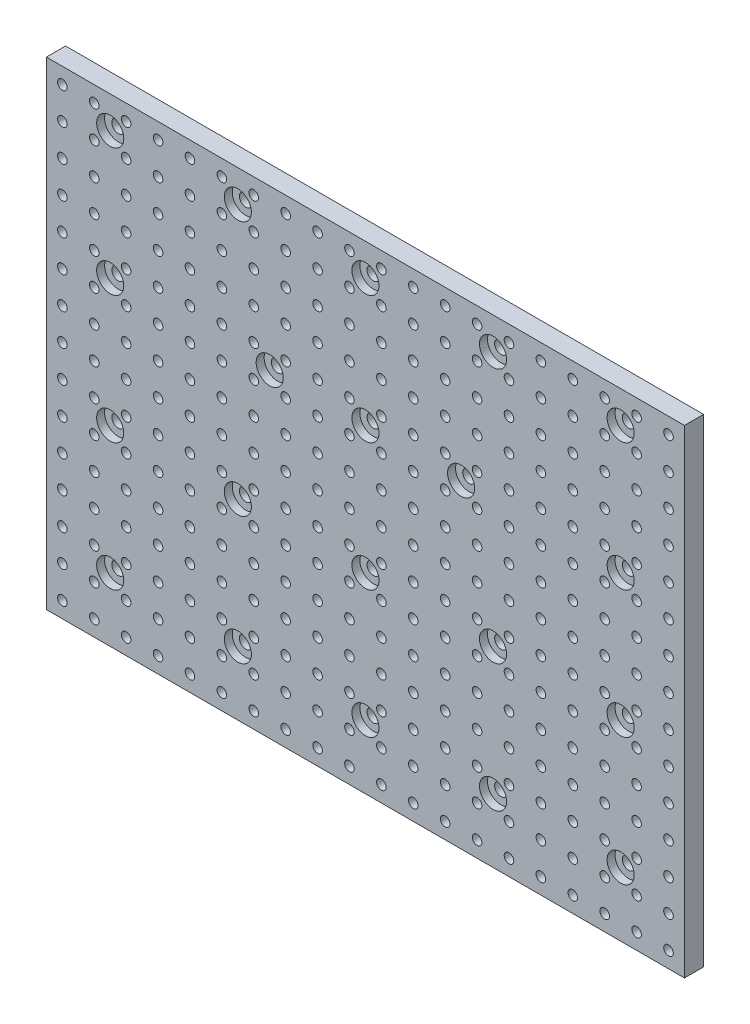
SolidWorks part; units mm, degrees
ref_plane "Front Plane" through (0, 0, 0) normal (0, 0, 1) x (1, 0, 0)
ref_plane "Top Plane" through (0, 0, 0) normal (0, 1, 0) x (1, 0, 0)
ref_plane "Right Plane" through (0, 0, 0) normal (1, 0, 0) x (0, 0, -1)
sketch "Sketch1" plane through (0, 0, 0) normal (0, 0, 1) x (1, 0, 0)
  line L1 (-200, 150) -> (200, 150)
  line L2 (-200, 150) -> (-200, -150)
  line L3 (-200, -150) -> (200, -150)
  line L4 (200, 150) -> (200, -150)
  line L5 (0, -150) -> (0, 150) construction
  line L6 (-200, 0) -> (200, 0) construction
  point P0 (0, 0)
  dimension "D1" = 300
  dimension "D2" = 400
extrude "Boss-Extrude1" add sketch "Sketch1" along normal blind 12
sketch "Sketch3" plane through (0, 0, 12) normal (0, 0, 1) x (1, 0, 0)
  circle A0 centre (-116, 92.75) radius 5
  circle A1 centre (-84, 92.75) radius 5
  circle A2 centre (-116, 56.75) radius 5
  circle A3 centre (-84, 56.75) radius 5
  circle A4 centre (84, 92.75) radius 5
  circle A5 centre (116, 92.75) radius 5
  circle A6 centre (84, 56.75) radius 5
  circle A7 centre (116, 56.75) radius 5
  circle A8 centre (116, -56.75) radius 5
  circle A9 centre (84, -56.75) radius 5
  circle A10 centre (84, -92.75) radius 5
  circle A11 centre (116, -92.75) radius 5
  circle A12 centre (-84, -92.75) radius 5
  circle A13 centre (-116, -92.75) radius 5
  circle A14 centre (-116, -56.75) radius 5
  circle A15 centre (-84, -56.75) radius 5
sketch "Sketch5" plane through (0, 0, 12) normal (0, 0, 1) x (1, 0, 0)
  line L0 (-190, 140) -> (-170, 140) construction
  line L1 (-190, 140) -> (-190, 120) construction
  circle A0 centre (-190, 140) radius 3
  circle A1 centre (-170, 140) radius 3
  circle A2 centre (-150, 140) radius 3
  circle A3 centre (-130, 140) radius 3
  circle A4 centre (-110, 140) radius 3
  circle A5 centre (-90, 140) radius 3
  circle A6 centre (-70, 140) radius 3
  circle A7 centre (-50, 140) radius 3
  circle A8 centre (-30, 140) radius 3
  circle A9 centre (-10, 140) radius 3
  circle A10 centre (10, 140) radius 3
  circle A11 centre (30, 140) radius 3
  circle A12 centre (50, 140) radius 3
  circle A13 centre (70, 140) radius 3
  circle A14 centre (90, 140) radius 3
  circle A15 centre (110, 140) radius 3
  circle A16 centre (130, 140) radius 3
  circle A17 centre (150, 140) radius 3
  circle A18 centre (170, 140) radius 3
  circle A19 centre (190, 140) radius 3
  circle A20 centre (-170, 120) radius 3
  circle A21 centre (-150, 120) radius 3
  circle A22 centre (-130, 120) radius 3
  circle A23 centre (-110, 120) radius 3
  circle A24 centre (-90, 120) radius 3
  circle A25 centre (-70, 120) radius 3
  circle A26 centre (-50, 120) radius 3
  circle A27 centre (-30, 120) radius 3
  circle A28 centre (-10, 120) radius 3
  circle A29 centre (10, 120) radius 3
  circle A30 centre (30, 120) radius 3
  circle A31 centre (50, 120) radius 3
  circle A32 centre (70, 120) radius 3
  circle A33 centre (90, 120) radius 3
  circle A34 centre (110, 120) radius 3
  circle A35 centre (130, 120) radius 3
  circle A36 centre (150, 120) radius 3
  circle A37 centre (170, 120) radius 3
  circle A38 centre (190, 120) radius 3
  circle A39 centre (-170, 100) radius 3
  circle A40 centre (-150, 100) radius 3
  circle A41 centre (-130, 100) radius 3
  circle A42 centre (-110, 100) radius 3
  circle A43 centre (-90, 100) radius 3
  circle A44 centre (-70, 100) radius 3
  circle A45 centre (-50, 100) radius 3
  circle A46 centre (-30, 100) radius 3
  circle A47 centre (-10, 100) radius 3
  circle A48 centre (10, 100) radius 3
  circle A49 centre (30, 100) radius 3
  circle A50 centre (50, 100) radius 3
  circle A51 centre (70, 100) radius 3
  circle A52 centre (90, 100) radius 3
  circle A53 centre (110, 100) radius 3
  circle A54 centre (130, 100) radius 3
  circle A55 centre (150, 100) radius 3
  circle A56 centre (170, 100) radius 3
  circle A57 centre (190, 100) radius 3
  circle A58 centre (-170, 80) radius 3
  circle A59 centre (-150, 80) radius 3
  circle A60 centre (-130, 80) radius 3
  circle A61 centre (-110, 80) radius 3
  circle A62 centre (-90, 80) radius 3
  circle A63 centre (-70, 80) radius 3
  circle A64 centre (-50, 80) radius 3
  circle A65 centre (-30, 80) radius 3
  circle A66 centre (-10, 80) radius 3
  circle A67 centre (10, 80) radius 3
  circle A68 centre (30, 80) radius 3
  circle A69 centre (50, 80) radius 3
  circle A70 centre (70, 80) radius 3
  circle A71 centre (90, 80) radius 3
  circle A72 centre (110, 80) radius 3
  circle A73 centre (130, 80) radius 3
  circle A74 centre (150, 80) radius 3
  circle A75 centre (170, 80) radius 3
  circle A76 centre (190, 80) radius 3
  circle A77 centre (-170, 60) radius 3
  circle A78 centre (-150, 60) radius 3
  circle A79 centre (-130, 60) radius 3
  circle A80 centre (-110, 60) radius 3
  circle A81 centre (-90, 60) radius 3
  circle A82 centre (-70, 60) radius 3
  circle A83 centre (-50, 60) radius 3
  circle A84 centre (-30, 60) radius 3
  circle A85 centre (-10, 60) radius 3
  circle A86 centre (10, 60) radius 3
  circle A87 centre (30, 60) radius 3
  circle A88 centre (50, 60) radius 3
  circle A89 centre (70, 60) radius 3
  circle A90 centre (90, 60) radius 3
  circle A91 centre (110, 60) radius 3
  circle A92 centre (130, 60) radius 3
  circle A93 centre (150, 60) radius 3
  circle A94 centre (170, 60) radius 3
  circle A95 centre (190, 60) radius 3
  circle A96 centre (-170, 40) radius 3
  circle A97 centre (-150, 40) radius 3
  circle A98 centre (-130, 40) radius 3
  circle A99 centre (-110, 40) radius 3
  circle A100 centre (-90, 40) radius 3
  circle A101 centre (-70, 40) radius 3
  circle A102 centre (-50, 40) radius 3
  circle A103 centre (-30, 40) radius 3
  circle A104 centre (-10, 40) radius 3
  circle A105 centre (10, 40) radius 3
  circle A106 centre (30, 40) radius 3
  circle A107 centre (50, 40) radius 3
  circle A108 centre (70, 40) radius 3
  circle A109 centre (90, 40) radius 3
  circle A110 centre (110, 40) radius 3
  circle A111 centre (130, 40) radius 3
  circle A112 centre (150, 40) radius 3
  circle A113 centre (170, 40) radius 3
  circle A114 centre (190, 40) radius 3
  circle A115 centre (-170, 20) radius 3
  circle A116 centre (-150, 20) radius 3
  circle A117 centre (-130, 20) radius 3
  circle A118 centre (-110, 20) radius 3
  circle A119 centre (-90, 20) radius 3
  circle A120 centre (-70, 20) radius 3
  circle A121 centre (-50, 20) radius 3
  circle A122 centre (-30, 20) radius 3
  circle A123 centre (-10, 20) radius 3
  circle A124 centre (10, 20) radius 3
  circle A125 centre (30, 20) radius 3
  circle A126 centre (50, 20) radius 3
  circle A127 centre (70, 20) radius 3
  circle A128 centre (90, 20) radius 3
  circle A129 centre (110, 20) radius 3
  circle A130 centre (130, 20) radius 3
  circle A131 centre (150, 20) radius 3
  circle A132 centre (170, 20) radius 3
  circle A133 centre (190, 20) radius 3
  circle A134 centre (-170, 0) radius 3
  circle A135 centre (-150, 0) radius 3
  circle A136 centre (-130, 0) radius 3
  circle A137 centre (-110, 0) radius 3
  circle A138 centre (-90, 0) radius 3
  circle A139 centre (-70, 0) radius 3
  circle A140 centre (-50, 0) radius 3
  circle A141 centre (-30, 0) radius 3
  circle A142 centre (-10, 0) radius 3
  circle A143 centre (10, 0) radius 3
  circle A144 centre (30, 0) radius 3
  circle A145 centre (50, 0) radius 3
  circle A146 centre (70, 0) radius 3
  circle A147 centre (90, 0) radius 3
  circle A148 centre (110, 0) radius 3
  circle A149 centre (130, 0) radius 3
  circle A150 centre (150, 0) radius 3
  circle A151 centre (170, 0) radius 3
  circle A152 centre (190, 0) radius 3
  circle A153 centre (-170, -20) radius 3
  circle A154 centre (-150, -20) radius 3
  circle A155 centre (-130, -20) radius 3
  circle A156 centre (-110, -20) radius 3
  circle A157 centre (-90, -20) radius 3
  circle A158 centre (-70, -20) radius 3
  circle A159 centre (-50, -20) radius 3
  circle A160 centre (-30, -20) radius 3
  circle A161 centre (-10, -20) radius 3
  circle A162 centre (10, -20) radius 3
  circle A163 centre (30, -20) radius 3
  circle A164 centre (50, -20) radius 3
  circle A165 centre (70, -20) radius 3
  circle A166 centre (90, -20) radius 3
  circle A167 centre (110, -20) radius 3
  circle A168 centre (130, -20) radius 3
  circle A169 centre (150, -20) radius 3
  circle A170 centre (170, -20) radius 3
  circle A171 centre (190, -20) radius 3
  circle A172 centre (-170, -40) radius 3
  circle A173 centre (-150, -40) radius 3
  circle A174 centre (-130, -40) radius 3
  circle A175 centre (-110, -40) radius 3
  circle A176 centre (-90, -40) radius 3
  circle A177 centre (-70, -40) radius 3
  circle A178 centre (-50, -40) radius 3
  circle A179 centre (-30, -40) radius 3
  circle A180 centre (-10, -40) radius 3
  circle A181 centre (10, -40) radius 3
  circle A182 centre (30, -40) radius 3
  circle A183 centre (50, -40) radius 3
  circle A184 centre (70, -40) radius 3
  circle A185 centre (90, -40) radius 3
  circle A186 centre (110, -40) radius 3
  circle A187 centre (130, -40) radius 3
  circle A188 centre (150, -40) radius 3
  circle A189 centre (170, -40) radius 3
  circle A190 centre (190, -40) radius 3
  circle A191 centre (-170, -60) radius 3
  circle A192 centre (-150, -60) radius 3
  circle A193 centre (-130, -60) radius 3
  circle A194 centre (-110, -60) radius 3
  circle A195 centre (-90, -60) radius 3
  circle A196 centre (-70, -60) radius 3
  circle A197 centre (-50, -60) radius 3
  circle A198 centre (-30, -60) radius 3
  circle A199 centre (-10, -60) radius 3
  circle A200 centre (10, -60) radius 3
  circle A201 centre (30, -60) radius 3
  circle A202 centre (50, -60) radius 3
  circle A203 centre (70, -60) radius 3
  circle A204 centre (90, -60) radius 3
  circle A205 centre (110, -60) radius 3
  circle A206 centre (130, -60) radius 3
  circle A207 centre (150, -60) radius 3
  circle A208 centre (170, -60) radius 3
  circle A209 centre (190, -60) radius 3
  circle A210 centre (-170, -80) radius 3
  circle A211 centre (-150, -80) radius 3
  circle A212 centre (-130, -80) radius 3
  circle A213 centre (-110, -80) radius 3
  circle A214 centre (-90, -80) radius 3
  circle A215 centre (-70, -80) radius 3
  circle A216 centre (-50, -80) radius 3
  circle A217 centre (-30, -80) radius 3
  circle A218 centre (-10, -80) radius 3
  circle A219 centre (10, -80) radius 3
  circle A220 centre (30, -80) radius 3
  circle A221 centre (50, -80) radius 3
  circle A222 centre (70, -80) radius 3
  circle A223 centre (90, -80) radius 3
  circle A224 centre (110, -80) radius 3
  circle A225 centre (130, -80) radius 3
  circle A226 centre (150, -80) radius 3
  circle A227 centre (170, -80) radius 3
  circle A228 centre (190, -80) radius 3
  circle A229 centre (-170, -100) radius 3
  circle A230 centre (-150, -100) radius 3
  circle A231 centre (-130, -100) radius 3
  circle A232 centre (-110, -100) radius 3
  circle A233 centre (-90, -100) radius 3
  circle A234 centre (-70, -100) radius 3
  circle A235 centre (-50, -100) radius 3
  circle A236 centre (-30, -100) radius 3
  circle A237 centre (-10, -100) radius 3
  circle A238 centre (10, -100) radius 3
  circle A239 centre (30, -100) radius 3
  circle A240 centre (50, -100) radius 3
  circle A241 centre (70, -100) radius 3
  circle A242 centre (90, -100) radius 3
  circle A243 centre (110, -100) radius 3
  circle A244 centre (130, -100) radius 3
  circle A245 centre (150, -100) radius 3
  circle A246 centre (170, -100) radius 3
  circle A247 centre (190, -100) radius 3
  circle A248 centre (-170, -120) radius 3
  circle A249 centre (-150, -120) radius 3
  circle A250 centre (-130, -120) radius 3
  circle A251 centre (-110, -120) radius 3
  circle A252 centre (-90, -120) radius 3
  circle A253 centre (-70, -120) radius 3
  circle A254 centre (-50, -120) radius 3
  circle A255 centre (-30, -120) radius 3
  circle A256 centre (-10, -120) radius 3
  circle A257 centre (10, -120) radius 3
  circle A258 centre (30, -120) radius 3
  circle A259 centre (50, -120) radius 3
  circle A260 centre (70, -120) radius 3
  circle A261 centre (90, -120) radius 3
  circle A262 centre (110, -120) radius 3
  circle A263 centre (130, -120) radius 3
  circle A264 centre (150, -120) radius 3
  circle A265 centre (170, -120) radius 3
  circle A266 centre (190, -120) radius 3
  circle A267 centre (-170, -140) radius 3
  circle A268 centre (-150, -140) radius 3
  circle A269 centre (-130, -140) radius 3
  circle A270 centre (-110, -140) radius 3
  circle A271 centre (-90, -140) radius 3
  circle A272 centre (-70, -140) radius 3
  circle A273 centre (-50, -140) radius 3
  circle A274 centre (-30, -140) radius 3
  circle A275 centre (-10, -140) radius 3
  circle A276 centre (10, -140) radius 3
  circle A277 centre (30, -140) radius 3
  circle A278 centre (50, -140) radius 3
  circle A279 centre (70, -140) radius 3
  circle A280 centre (90, -140) radius 3
  circle A281 centre (110, -140) radius 3
  circle A282 centre (130, -140) radius 3
  circle A283 centre (150, -140) radius 3
  circle A284 centre (170, -140) radius 3
  circle A285 centre (190, -140) radius 3
  circle A286 centre (-190, 120) radius 3
  circle A287 centre (-190, 100) radius 3
  circle A288 centre (-190, 80) radius 3
  circle A289 centre (-190, 60) radius 3
  circle A290 centre (-190, 40) radius 3
  circle A291 centre (-190, 20) radius 3
  circle A292 centre (-190, 0) radius 3
  circle A293 centre (-190, -20) radius 3
  circle A294 centre (-190, -40) radius 3
  circle A295 centre (-190, -60) radius 3
  circle A296 centre (-190, -80) radius 3
  circle A297 centre (-190, -100) radius 3
  circle A298 centre (-190, -120) radius 3
  circle A299 centre (-190, -140) radius 3
  dimension "D1" = 20
  dimension "D3" = 20
  dimension "D4" = 20
  dimension "D2" = 15
extrude "Cut-Extrude1" cut sketch "Sketch5" against normal through all
sketch "Sketch6" plane through (0, 0, 12) normal (0, 0, 1) x (1, 0, 0)
  line L0 (-160, 130) -> (-80, 130) construction
  circle A0 centre (-160, 130) radius 4
  circle A1 centre (-80, 130) radius 4
  circle A2 centre (0, 130) radius 4
  circle A3 centre (80, 130) radius 4
  circle A4 centre (160, 130) radius 4
  circle A25 centre (-160, 50) radius 4
  circle A27 centre (0, 50) radius 4
  circle A29 centre (160, 50) radius 4
  circle A30 centre (-160, -30) radius 4
  circle A31 centre (-80, -30) radius 4
  circle A32 centre (0, -30) radius 4
  circle A33 centre (80, -30) radius 4
  circle A34 centre (160, -30) radius 4
  circle A35 centre (-160, -110) radius 4
  circle A36 centre (-80, -110) radius 4
  circle A37 centre (0, -110) radius 4
  circle A38 centre (80, -110) radius 4
  circle A39 centre (160, -110) radius 4
  circle A40 centre (-60, 50) radius 4
  circle A41 centre (-80, 50) radius 4 [skipped]
  circle A42 centre (60, 50) radius 4
  circle A43 centre (80, 50) radius 4 [skipped]
  dimension "D1" = 5
  dimension "D3" = 80
  dimension "D2" = 4
extrude "Cut-Extrude2" cut sketch "Sketch6" against normal through all
sketch "Sketch7" plane through (0, 0, 12) normal (0, 0, 1) x (1, 0, 0)
  circle A0 centre (-160, 130) radius 8.5
  circle A1 centre (-80, 130) radius 8.5
  circle A2 centre (0, 130) radius 8.5
  circle A3 centre (80, 130) radius 8.5
  circle A4 centre (160, 130) radius 8.5
  circle A5 centre (-160, 50) radius 8.5
  circle A6 centre (-60, 50) radius 8.5
  circle A7 centre (0, 50) radius 8.5
  circle A8 centre (60, 50) radius 8.5
  circle A9 centre (160, 50) radius 8.5
  circle A10 centre (-160, -30) radius 8.5
  circle A11 centre (-80, -30) radius 8.5
  circle A12 centre (0, -30) radius 8.5
  circle A13 centre (80, -30) radius 8.5
  circle A14 centre (160, -30) radius 8.5
  circle A15 centre (-160, -110) radius 8.5
  circle A16 centre (-80, -110) radius 8.5
  circle A17 centre (0, -110) radius 8.5
  circle A18 centre (80, -110) radius 8.5
  circle A19 centre (160, -110) radius 8.5
extrude "Cut-Extrude3" cut sketch "Sketch7" against normal blind 5
